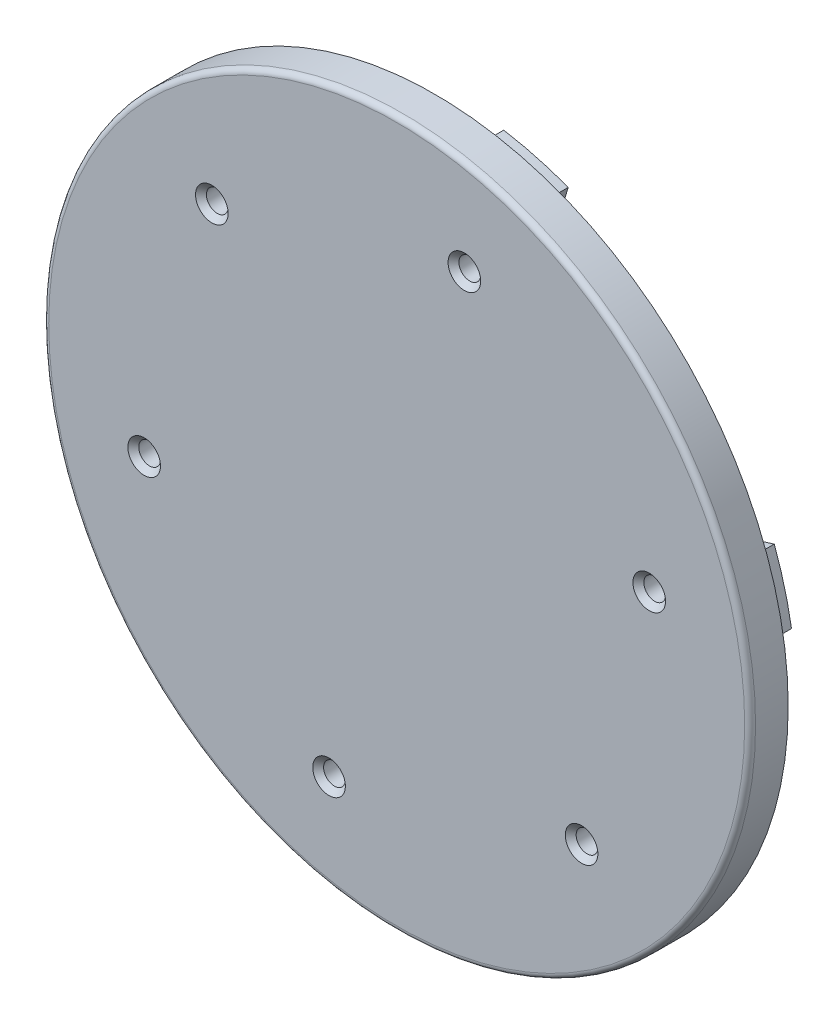
SolidWorks part; units mm, degrees
ref_plane "前视基准面" through (0, 0, 0) normal (0, 0, 1) x (1, 0, 0)
ref_plane "上视基准面" through (0, 0, 0) normal (0, 1, 0) x (1, 0, 0)
ref_plane "右视基准面" through (0, 0, 0) normal (1, 0, 0) x (0, 0, -1)
sketch "草图1" plane through (0, 0, 0) normal (0, 0, 1) x (1, 0, 0)
  line L24 (10.6844, 63.6089) -> (3.9198, 33.4713)
  line L25 (10.6844, 63.6089) -> (3.9198, 33.4713)
  line L26 (-20.0302, 27.1013) -> (-41.0574, 49.7447)
  line L27 (-20.0302, 27.1013) -> (-41.0574, 49.7447)
  line L28 (-49.7447, 41.0574) -> (-27.0271, 20.1302)
  line L29 (-49.7447, 41.0574) -> (-27.0271, 20.1302)
  line L30 (-33.4855, -3.796) -> (-63.6089, -10.6844)
  line L31 (-33.4855, -3.796) -> (-63.6089, -10.6844)
  line L32 (-60.4291, -22.5515) -> (-30.9468, -13.341)
  line L33 (-60.4291, -22.5515) -> (-30.9468, -13.341)
  line L34 (-13.4553, -30.8973) -> (-22.5515, -60.4291)
  line L35 (-13.4553, -30.8973) -> (-22.5515, -60.4291)
  line L36 (-10.6844, -63.6089) -> (-3.9198, -33.4713)
  line L37 (-10.6844, -63.6089) -> (-3.9198, -33.4713)
  line L38 (20.0302, -27.1013) -> (41.0574, -49.7447)
  line L39 (20.0302, -27.1013) -> (41.0574, -49.7447)
  line L40 (49.7447, -41.0574) -> (27.0271, -20.1302)
  line L41 (49.7447, -41.0574) -> (27.0271, -20.1302)
  line L42 (33.4855, 3.796) -> (63.6089, 10.6844)
  line L43 (33.4855, 3.796) -> (63.6089, 10.6844)
  line L44 (60.4291, 22.5515) -> (30.9468, 13.341)
  line L45 (60.4291, 22.5515) -> (30.9468, 13.341)
  line L46 (13.4553, 30.8973) -> (22.5515, 60.4291)
  line L47 (13.4553, 30.8973) -> (22.5515, 60.4291)
  arc A1 (3.9198, 33.4713) -> (-20.0302, 27.1013) centre (0, 0) ccw
  circle A4 centre (0, 0) radius 18.98
  arc A28 (3.9198, 33.4713) -> (-20.0302, 27.1013) centre (0, 0) ccw
  arc A29 (-41.0574, 49.7447) -> (-49.7447, 41.0574) centre (0, 0) ccw
  arc A30 (-41.0574, 49.7447) -> (-49.7447, 41.0574) centre (0, 0) ccw
  arc A31 (-27.0271, 20.1302) -> (-33.4855, -3.796) centre (0, 0) ccw
  arc A32 (-27.0271, 20.1302) -> (-33.4855, -3.796) centre (0, 0) ccw
  arc A33 (-63.6089, -10.6844) -> (-60.4291, -22.5515) centre (0, 0) ccw
  arc A34 (-63.6089, -10.6844) -> (-60.4291, -22.5515) centre (0, 0) ccw
  arc A35 (-30.9468, -13.341) -> (-13.4553, -30.8973) centre (0, 0) ccw
  arc A36 (-30.9468, -13.341) -> (-13.4553, -30.8973) centre (0, 0) ccw
  arc A37 (-22.5515, -60.4291) -> (-10.6844, -63.6089) centre (0, 0) ccw
  arc A38 (-22.5515, -60.4291) -> (-10.6844, -63.6089) centre (0, 0) ccw
  arc A39 (-3.9198, -33.4713) -> (20.0302, -27.1013) centre (0, 0) ccw
  arc A40 (-3.9198, -33.4713) -> (20.0302, -27.1013) centre (0, 0) ccw
  arc A41 (41.0574, -49.7447) -> (49.7447, -41.0574) centre (0, 0) ccw
  arc A42 (41.0574, -49.7447) -> (49.7447, -41.0574) centre (0, 0) ccw
  arc A43 (27.0271, -20.1302) -> (33.4855, 3.796) centre (0, 0) ccw
  arc A44 (27.0271, -20.1302) -> (33.4855, 3.796) centre (0, 0) ccw
  arc A45 (63.6089, 10.6844) -> (60.4291, 22.5515) centre (0, 0) ccw
  arc A46 (63.6089, 10.6844) -> (60.4291, 22.5515) centre (0, 0) ccw
  arc A47 (30.9468, 13.341) -> (13.4553, 30.8973) centre (0, 0) ccw
  arc A48 (30.9468, 13.341) -> (13.4553, 30.8973) centre (0, 0) ccw
  arc A49 (22.5515, 60.4291) -> (10.6844, 63.6089) centre (0, 0) ccw
  arc A50 (22.5515, 60.4291) -> (10.6844, 63.6089) centre (0, 0) ccw
  dimension "D1" = 0
extrude "凸台-拉伸1" add sketch "草图1" along normal blind 2
sketch "草图2" plane through (0, 0, 2) normal (0, 0, 1) x (1, 0, 0)
  circle A2 centre (0, 0) radius 65
  dimension "D1" = 130
extrude "凸台-拉伸2" add sketch "草图2" along normal blind 7
sketch "草图4" plane through (0, 0, 0) normal (0, 0, -1) x (-1, 0, 0)
  line L0 (-3.9198, 33.4713) -> (-10.6844, 63.6089) construction
  line L1 (-3.9198, 33.4713) -> (-10.6844, 63.6089)
  line L2 (41.0574, 49.7447) -> (20.0302, 27.1013) construction
  line L3 (41.0574, 49.7447) -> (20.0302, 27.1013)
  line L4 (63.6089, -10.6844) -> (33.4855, -3.796) construction
  line L5 (63.6089, -10.6844) -> (33.4855, -3.796)
  line L7 (63.6089, -10.6844) -> (49.7447, 41.0574)
  line L8 (27.0271, 20.1302) -> (49.7447, 41.0574) construction
  line L9 (27.0271, 20.1302) -> (49.7447, 41.0574)
  line L10 (30.9468, -13.341) -> (60.4291, -22.5515) construction
  line L11 (30.9468, -13.341) -> (60.4291, -22.5515)
  line L12 (22.5515, -60.4291) -> (13.4553, -30.8973) construction
  line L13 (22.5515, -60.4291) -> (13.4553, -30.8973)
  line L14 (-30.9468, 13.341) -> (-60.4291, 22.5515) construction
  line L15 (-22.5515, 60.4291) -> (-13.4553, 30.8973) construction
  line L16 (-30.9468, 13.341) -> (-60.4291, 22.5515)
  line L17 (-22.5515, 60.4291) -> (-13.4553, 30.8973)
  line L18 (-63.6089, 10.6844) -> (-33.4855, 3.796) construction
  line L19 (-27.0271, -20.1302) -> (-49.7447, -41.0574) construction
  line L20 (-63.6089, 10.6844) -> (-33.4855, 3.796)
  line L21 (-27.0271, -20.1302) -> (-49.7447, -41.0574)
  line L22 (-41.0574, -49.7447) -> (-20.0302, -27.1013) construction
  line L23 (3.9198, -33.4713) -> (10.6844, -63.6089) construction
  line L24 (3.9198, -33.4713) -> (10.6844, -63.6089)
  line L25 (-41.0574, -49.7447) -> (-20.0302, -27.1013)
  arc A0 (20.0302, 27.1013) -> (-3.9198, 33.4713) centre (0, 0) ccw construction
  arc A1 (20.0302, 27.1013) -> (-3.9198, 33.4713) centre (0, 0) ccw
  arc A2 (41.0574, 49.7447) -> (-10.6844, 63.6089) centre (0, 0) ccw construction
  arc A3 (41.0574, 49.7447) -> (-10.6844, 63.6089) centre (0, 0) ccw
  arc A5 (27.0271, 20.1302) -> (33.4855, -3.796) centre (0, 0) ccw
  arc A6 (33.4855, -3.796) -> (27.0271, 20.1302) centre (0, 0) ccw construction
  arc A7 (33.4855, -3.796) -> (27.0271, 20.1302) centre (0, 0) ccw
  arc A8 (33.4855, -3.796) -> (27.0271, 20.1302) centre (0, 0) ccw construction
  arc A9 (33.4855, -3.796) -> (27.0271, 20.1302) centre (0, 0) ccw
  arc A10 (63.6089, -10.6844) -> (49.7447, 41.0574) centre (0, 0) ccw construction
  arc A11 (63.6089, -10.6844) -> (49.7447, 41.0574) centre (0, 0) ccw
  arc A12 (63.6089, -10.6844) -> (49.7447, 41.0574) centre (0, 0) ccw construction
  arc A13 (63.6089, -10.6844) -> (49.7447, 41.0574) centre (0, 0) ccw
  arc A14 (13.4553, -30.8973) -> (30.9468, -13.341) centre (0, 0) ccw construction
  arc A15 (13.4553, -30.8973) -> (30.9468, -13.341) centre (0, 0) ccw
  arc A16 (22.5515, -60.4291) -> (60.4291, -22.5515) centre (0, 0) ccw construction
  arc A17 (22.5515, -60.4291) -> (60.4291, -22.5515) centre (0, 0) ccw
  arc A18 (-22.5515, 60.4291) -> (-60.4291, 22.5515) centre (0, 0) ccw construction
  arc A19 (-13.4553, 30.8973) -> (-30.9468, 13.341) centre (0, 0) ccw construction
  arc A20 (-22.5515, 60.4291) -> (-60.4291, 22.5515) centre (0, 0) ccw
  arc A21 (-13.4553, 30.8973) -> (-30.9468, 13.341) centre (0, 0) ccw
  arc A22 (-33.4855, 3.796) -> (-27.0271, -20.1302) centre (0, 0) ccw construction
  arc A23 (-63.6089, 10.6844) -> (-49.7447, -41.0574) centre (0, 0) ccw construction
  arc A24 (-33.4855, 3.796) -> (-27.0271, -20.1302) centre (0, 0) ccw
  arc A25 (-63.6089, 10.6844) -> (-49.7447, -41.0574) centre (0, 0) ccw
  arc A26 (-20.0302, -27.1013) -> (3.9198, -33.4713) centre (0, 0) ccw construction
  arc A27 (-41.0574, -49.7447) -> (10.6844, -63.6089) centre (0, 0) ccw construction
  arc A28 (-41.0574, -49.7447) -> (10.6844, -63.6089) centre (0, 0) ccw
  arc A29 (-20.0302, -27.1013) -> (3.9198, -33.4713) centre (0, 0) ccw
extrude "切除-拉伸1" cut sketch "草图4" against normal blind 7.8 rebuild error yes
sketch "草图5" plane through (0, 0, -18) normal (0, 0, -1) x (-1, 0, 0)
  circle A0 centre (34, 34) radius 0.95
  circle A1 centre (46.4449, -12.4449) radius 0.95
  circle A2 centre (12.4449, -46.4449) radius 0.95
  circle A3 centre (-34, -34) radius 0.95
  circle A4 centre (-46.4449, 12.4449) radius 0.95
  circle A5 centre (-12.4449, 46.4449) radius 0.95
extrude "切除-拉伸2" cut sketch "草图5" against normal blind 55
sketch "草图6" plane through (0, 0, 2) normal (0, 0, -1) x (-1, 0, 0)
  circle A0 centre (0, 0) radius 3.6
  dimension "D1" = 7.2
extrude "切除-拉伸3" cut sketch "草图6" against normal blind 6
sketch "草图8" plane through (0, 0, 2) normal (0, 0, -1) x (-1, 0, 0)
  circle A0 centre (0, 0) radius 6.6
  circle A2 centre (0, 0) radius 3.6 construction
  circle A3 centre (0, 0) radius 18.98
  dimension "D1" = 3
extrude "切除-拉伸4" cut sketch "草图8" against normal blind 6
sketch "草图10" plane through (-52.1928, 13.985, 0) normal (0.9659, -0.2588, 0) x (0, 0, -1)
  line L1 (0, 0) -> (-7.8, 0) construction
  line L2 (0, -10.2632) -> (0, 10.2632) construction
  line L3 (-7.8, -10.2632) -> (-7.8, 10.2632) construction
  line L5 (-7.8, 2.5) -> (0, 2.5)
  line L7 (-7.8, -2.5) -> (0, -2.5)
  line L8 (0, 2.5) -> (0, -2.5)
  line L9 (-7.8, 0) -> (0, -2.5) construction
  line L10 (-7.8, 0) -> (0, 2.5) construction
  line L12 (-7.8, 2.5) -> (-7.8, -2.5)
  line L13 (0, -10.2632) -> (0, 10.2632) construction
  dimension "D1" = 0
  dimension "D2" = 0
extrude "切除-拉伸5" cut sketch "草图10" along normal blind 53
sketch "草图11" plane through (0, 0, 0) normal (0, 0, -1) x (-1, 0, 0)
  circle A0 centre (0, 0) radius 55
  circle A1 centre (0, 0) radius 55.7
extrude "切除-拉伸6" cut sketch "草图11" against normal up to surface (2 mm away) up to face at (65, 0, 2)
sketch "草图12" plane through (0, 0, 0) normal (0, 0, -1) x (-1, 0, 0)
  line L1 (49.5365, 23.8985) -> (54.8491, 4.0715)
  line L2 (49.5365, 23.8985) -> (54.8491, 4.0715)
  arc A1 (54.8491, 4.0715) -> (49.5365, 23.8985) centre (0, 0) ccw
  arc A2 (54.8491, 4.0715) -> (49.5365, 23.8985) centre (0, 0) ccw
  dimension "D1" = 0
extrude "切除-拉伸7" cut sketch "草图12" against normal up to surface (2 mm away) rebuild error yes up to face at (15.525, 57.906, 2)
fillet "圆角2" radius 1 1 edges at (65, 0, 9)
chamfer "倒角3" distance 3 angle 45 1 edges at (-6.6, 0, 8)
sketch "草图13" plane through (0, 0, 9) normal (0, 0, 1) x (1, 0, 0)
  circle A18 centre (-34, 34) radius 2
  circle A19 centre (-46.4449, -12.4449) radius 2
  circle A20 centre (-12.4449, -46.4449) radius 2
  circle A21 centre (34, -34) radius 2
  circle A22 centre (46.4449, 12.4449) radius 2
  circle A23 centre (12.4449, 46.4449) radius 2
  dimension "D1" = 4
  dimension "D2" = 4
  dimension "D3" = 4
  dimension "D4" = 4
  dimension "D5" = 4
  dimension "D6" = 4
extrude "切除-拉伸8" cut sketch "草图13" against normal blind 5
chamfer "倒角4" distance 1 angle 45 1 edges at (3.4773, -0.9317, 2)
chamfer "倒角5" distance 1 angle 45 6 edges at (-10.4449, -46.4449, 9) (36, -34, 9) (48.4449, 12.4449, 9) (14.4449, 46.4449, 9) (-32, 34, 9) (-44.4449, -12.4449, 9)
